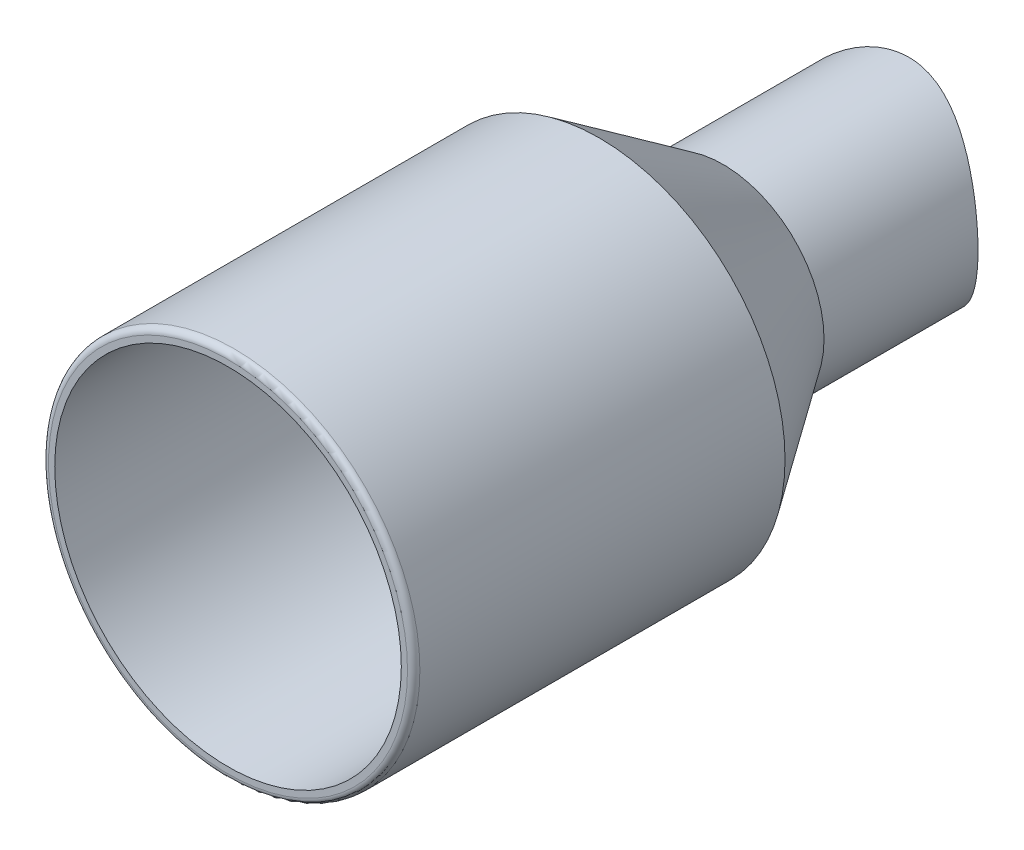
SolidWorks part; units mm, degrees
ref_plane "Front Plane" through (0, 0, 0) normal (0, 0, 1) x (1, 0, 0)
ref_plane "Top Plane" through (0, 0, 0) normal (0, 1, 0) x (1, 0, 0)
ref_plane "Right Plane" through (0, 0, 0) normal (1, 0, 0) x (0, 0, -1)
sketch "Sketch1" plane through (0, 0, 0) normal (0, 0, 1) x (1, 0, 0)
  circle A0 centre (0, 0) radius 15
  circle A1 centre (0, 0) radius 14
  dimension "D1" = 30
  dimension "D2" = 1
extrude "Boss-Extrude1" add sketch "Sketch1" along normal blind 30
sketch "Sketch2" plane through (0, 0, 0) normal (0, 0, -1) x (-1, 0, 0)
  circle A0 centre (0, 0) radius 15 construction
  point P0 (0, 0)
  point P1 (0, 15)
sketch "Sketch4" plane through (0, 0, 30) normal (0, 0, 1) x (1, 0, 0)
  point P0 (0, 15)
ref_plane "Plane1" through (0, 0, 0) normal (1, 0, 0) x (0, 0, -1)
sketch "Sketch5" plane through (0, 0, 0) normal (1, 0, 0) x (0, 0, -1)
  line L0 (0, 0) -> (30, 0) construction
  line L3 (10, 8.15) -> (0, 15)
  line L4 (0, -15) -> (0, 15) construction
  line L5 (0, 15) -> (0, 14)
  line L6 (0, 14) -> (10, 7.15)
  line L7 (10, 7.15) -> (10, 8.15)
  line L10 (10, 8.15) -> (25, 8.15)
  line L11 (10, 8.15) -> (10, 7.15)
  line L12 (10, 7.15) -> (25, 7.15)
  line L13 (25, 8.15) -> (25, 7.15)
  dimension "D1" = 10
  dimension "D2" = 15
  dimension "D3" = 7.15
fillet "Fillet1" radius 0.5 1 edges at (15, 0, 30)
revolve "Revolve1" add sketch "Sketch5" angle 360 about L0 region at (0, 11.075, -5) region at (0, 7.65, -17.5)
sketch "Sketch6" plane through (0, 0, 0) normal (1, 0, 0) x (0, 0, -1)
  line L2 (25, 8.15) -> (25, -8.15) construction
  circle A0 centre (36.6893, 0) radius 14.25
  point P5 (25, 0)
  dimension "D1" = 28.5
extrude "Cut-Extrude1" cut sketch "Sketch6" against normal blind 10 and the other way blind 10
sketch "Sketch7" plane through (0, 0, 30) normal (0, 0, 1) x (1, 0, 0)
  line L1 (-5.15, -1) -> (-8.15, -1)
  line L2 (-5.15, -1) -> (-5.15, 1)
  line L3 (-5.15, 1) -> (-8.15, 1)
  line L4 (-8.15, -1) -> (-8.15, 1)
  line L5 (-5.15, -1) -> (-8.15, 1) construction
  line L6 (-5.15, 1) -> (-8.15, -1) construction
  line L7 (5.15, -1) -> (8.15, -1)
  line L8 (5.15, -1) -> (5.15, 1)
  line L9 (5.15, 1) -> (8.15, 1)
  line L10 (8.15, -1) -> (8.15, 1)
  line L11 (5.15, -1) -> (8.15, 1) construction
  line L12 (5.15, 1) -> (8.15, -1) construction
  circle A0 centre (0, 0) radius 8.15 construction
  circle A1 centre (0, 0) radius 8.15
  point P0 (-6.65, 0)
  point P5 (6.65, 0)
  dimension "D1" = 3
  dimension "D2" = 3
  dimension "D3" = 2
  dimension "D4" = 2
extrude "Boss-Extrude2" add sketch "Sketch7" against normal blind 7 from offset 40 contours L3 A1 L1 L2 | A1 L9 L8 L7 region at (-6.6398, 0, 30) region at (6.6398, 0, 30) offset against normal yes
chamfer "Chamfer1" distance 1 angle 45 2 edges at (-5.15, 0, -17) (5.15, 0, -17)
